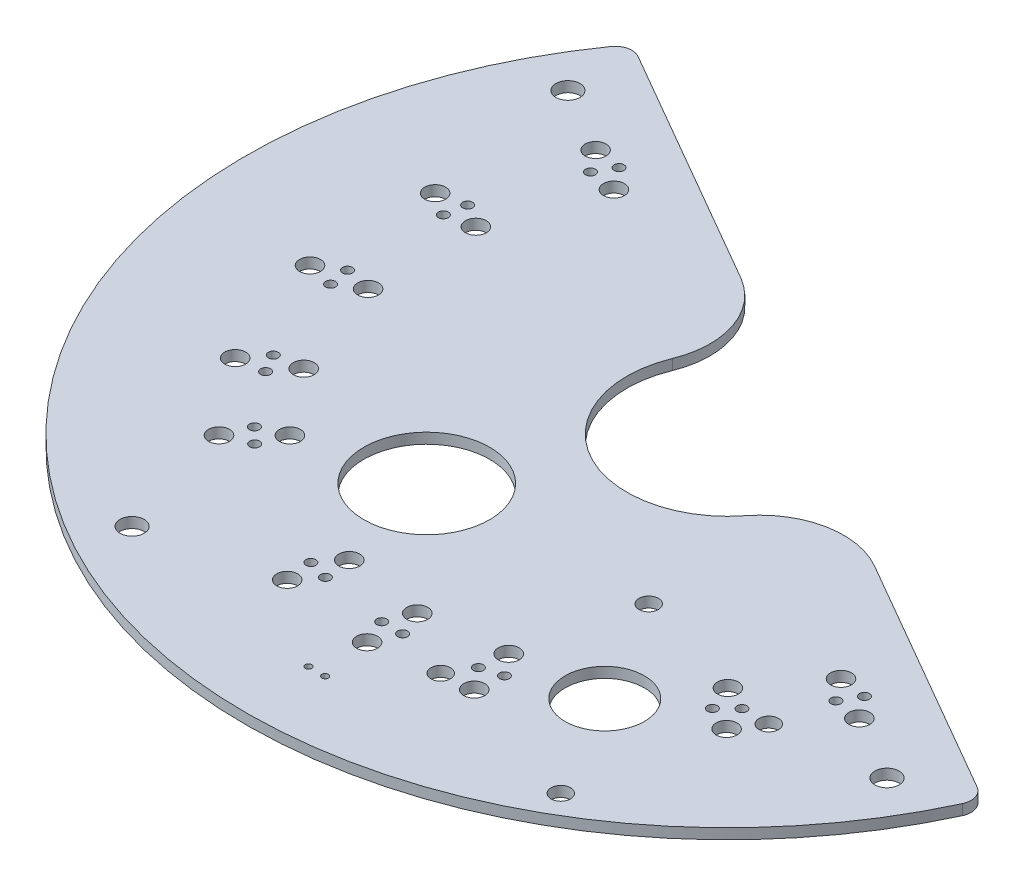
SolidWorks part; units mm, degrees
ref_plane "Front Plane" through (0, 0, 0) normal (0, 0, 1) x (1, 0, 0)
ref_plane "Top Plane" through (0, 0, 0) normal (0, 1, 0) x (1, 0, 0)
ref_plane "Right Plane" through (0, 0, 0) normal (1, 0, 0) x (0, 0, -1)
sketch "Sketch1" plane through (0, 0, 0) normal (0, 1, 0) x (1, 0, 0)
  line L0 (0, 50.8) -> (0, 59.6199) construction
  line L1 (0, 50.8) -> (11.3081, 50.8) construction
  line L2 (0, 0) -> (0, 47) construction
  line L3 (0, 0) -> (-46.286, 8.1615) construction
  line L4 (0, 0) -> (0, 47) construction
  line L5 (0, 0) -> (-46.286, -8.1615) construction
  line L6 (-35.6665, -35.9809) -> (-43.3836, -40.2586) construction
  line L7 (-13.202, -48.8223) -> (-8.5263, -41.3397) construction
  line L8 (34.9566, -37.7798) -> (30.8142, -29.9892) construction
  line L9 (12.3219, -50.1988) -> (12.3219, -41.3754) construction
  circle A0 centre (0, 0) radius 50.8 construction
  circle A1 centre (0, 0) radius 15.24
  circle A2 centre (0, 0) radius 73.025
  circle A3 centre (0, 50.8) radius 6.3 construction
  circle A4 centre (25.4, 43.9941) radius 6.3 construction
  circle A5 centre (43.9941, 25.4) radius 6.3 construction
  circle A6 centre (50.8, 0) radius 6.3 construction
  circle A7 centre (43.9941, -25.4) radius 6.3 construction
  circle A8 centre (25.4, -43.9941) radius 6.3 construction
  circle A9 centre (0, -50.8) radius 6.3 construction
  circle A10 centre (-25.4, -43.9941) radius 6.3 construction
  circle A11 centre (-43.9941, -25.4) radius 6.3 construction
  circle A12 centre (-50.8, 0) radius 6.3 construction
  circle A13 centre (-43.9941, 25.4) radius 6.3 construction
  circle A14 centre (-25.4, 43.9941) radius 6.3 construction
  circle A15 centre (0, 50.8) radius 1.585 construction
  circle A16 centre (-1.585, 50.8) radius 0.75
  circle A17 centre (1.585, 50.8) radius 0.75
  circle A18 centre (0, 50.8) radius 3.8 construction
  circle A19 centre (0, 54.6) radius 1.585
  circle A20 centre (0, 47) radius 1.585
  circle A21 centre (47.285, 27.3) radius 1.585
  circle A22 centre (43.2016, 26.7727) radius 0.75
  circle A23 centre (44.7866, 24.0273) radius 0.75
  circle A24 centre (40.7032, 23.5) radius 1.585
  circle A25 centre (47.285, -27.3) radius 1.585
  circle A26 centre (44.7866, -24.0273) radius 0.75
  circle A27 centre (43.2016, -26.7727) radius 0.75
  circle A28 centre (40.7032, -23.5) radius 1.585
  circle A29 centre (0, -54.6) radius 1.585
  circle A30 centre (1.585, -50.8) radius 0.75
  circle A31 centre (-1.585, -50.8) radius 0.75
  circle A32 centre (0, -47) radius 1.585
  circle A33 centre (-47.285, -27.3) radius 1.585
  circle A34 centre (-43.2016, -26.7727) radius 0.75
  circle A35 centre (-44.7866, -24.0273) radius 0.75
  circle A36 centre (-40.7032, -23.5) radius 1.585
  circle A37 centre (-47.285, 27.3) radius 1.585
  circle A38 centre (-44.7866, 24.0273) radius 0.75
  circle A39 centre (-43.2016, 26.7727) radius 0.75
  circle A40 centre (-40.7032, 23.5) radius 1.585
  circle A41 centre (25.4, 43.9941) radius 20
  circle A42 centre (-16.3207, -29.2429) radius 9.525
  circle A43 centre (25.4, -43.9941) radius 6
  circle A44 centre (-46.286, 8.1615) radius 1.585
  circle A45 centre (-50.3035, 7.2604) radius 0.75
  circle A46 centre (-49.753, 10.3822) radius 0.75
  circle A47 centre (-53.7705, 9.4812) radius 1.585
  circle A48 centre (-46.286, -8.1615) radius 1.585
  circle A49 centre (-49.753, -10.3822) radius 0.75
  circle A50 centre (-50.3035, -7.2604) radius 0.75
  circle A51 centre (-53.7705, -9.4812) radius 1.585
  circle A52 centre (-35.6625, -35.9801) radius 6.3 construction
  circle A53 centre (-35.6625, -35.9801) radius 1.585 construction
  circle A54 centre (-34.5403, -37.1015) radius 0.75
  circle A55 centre (-36.7991, -34.8717) radius 0.75
  circle A56 centre (-35.6625, -35.9801) radius 3.8 construction
  circle A57 centre (-38.371, -38.6691) radius 1.585
  circle A58 centre (-32.9869, -33.3052) radius 1.585
  circle A59 centre (-13.2051, -48.8249) radius 6.3 construction
  circle A60 centre (-13.2051, -48.8249) radius 1.585 construction
  circle A61 centre (-14.7302, -48.3882) radius 0.75
  circle A62 centre (-11.6736, -49.2433) radius 0.75
  circle A63 centre (-13.2051, -48.8249) radius 3.8 construction
  circle A64 centre (-12.1398, -45.16) radius 1.585
  circle A65 centre (-14.2484, -52.4617) radius 1.585
  circle A66 centre (35.9794, -36.0227) radius 6.3 construction
  circle A67 centre (35.9794, -36.0227) radius 1.585 construction
  circle A68 centre (34.8386, -37.1251) radius 0.75
  circle A69 centre (37.1074, -34.9056) radius 0.75
  circle A70 centre (35.9794, -36.0227) radius 3.8 construction
  circle A71 centre (33.3381, -33.2676) radius 1.585
  circle A72 centre (38.6072, -38.7446) radius 1.585
  circle A73 centre (13.281, -49.0556) radius 6.3 construction
  circle A74 centre (13.281, -49.0556) radius 1.585 construction
  circle A75 centre (11.7562, -49.4935) radius 0.75
  circle A76 centre (14.8015, -48.5989) radius 0.75
  circle A77 centre (13.281, -49.0556) radius 3.8 construction
  circle A78 centre (12.2423, -45.3831) radius 1.585
  circle A79 centre (14.3234, -52.6926) radius 1.585
  point P50 (0, 0)
  point P84 (0, 0)
  dimension "D1" = 12
  dimension "D2" = 101.6
  dimension "D3" = 3.17
  dimension "D4" = 1.5
  dimension "D5" = 7.6
  dimension "D6" = 6
  dimension "D7" = 3.17
  dimension "D8" = 40
  dimension "D9" = 19.05
  dimension "D10" = 12
  dimension "D11" = 146.05
  dimension "D12" = 30.48
  dimension "D14" = 80
  dimension "D16" = 100
  dimension "D13" = 2
  dimension "D15" = 2
extrude "Boss-Extrude1" add sketch "Sketch1" against normal blind 1.5875
sketch "Sketch2" plane through (0, 0, 0) normal (0, 1, 0) x (1, 0, 0)
  line L0 (0, 0) -> (0, 66.04) construction
  line L1 (0, 0) -> (-57.1923, 33.02) construction
  circle A0 centre (0, 0) radius 66.04 construction
  circle A1 centre (0, 66.04) radius 1.8288 construction
  circle A2 centre (-57.1923, 33.02) radius 1.8288
  circle A3 centre (33.02, 57.1923) radius 1.8288
  circle A4 centre (57.1923, -33.02) radius 1.8288
  circle A5 centre (-33.02, -57.1923) radius 1.8288
  point P17 (0, 0)
  dimension "D1" = 132.08
  dimension "D2" = 3.6576
  dimension "D3" = 2
  dimension "D4" = 60
  dimension "D5" = 4
extrude "Cut-Extrude1" cut sketch "Sketch2" against normal through all
sketch "Sketch3" plane through (0, 0, 0) normal (0, 1, 0) x (1, 0, 0)
  line L0 (-57.1923, 33.02) -> (57.1923, -33.02) construction
  line L1 (-59.5338, 44.6372) -> (68.4238, -29.2392)
  line L2 (-52.7473, 40.719) -> (61.6373, -25.321) construction
  arc A0 (68.4238, -29.2392) -> (-59.5338, 44.6372) centre (0, 0) ccw
  dimension "D1" = 8.89
extrude "Cut-Extrude2" cut sketch "Sketch3" against normal through all
fillet "Fillet1" radius 12.7 2 edges at (15.165, -0.7937, -1.5098) (-6.275, -0.7937, -13.8882)
fillet "Fillet2" radius 2.54 2 edges at (67.2161, -0.7937, 28.542) (-58.3261, -0.7937, -43.9399)
sketch "Sketch4" plane through (0, 0, 0) normal (0, 1, 0) x (1, 0, 0)
  line L0 (0, 0) -> (0, -73.025) construction
  arc A0 (-59.6949, 42.0615) -> (66.2738, -30.6666) centre (0, 0) ccw construction
  circle A1 centre (0, 0) radius 62.23 construction
  circle A2 centre (0, -62.23) radius 0.4953 construction
  circle A3 centre (1.27, -62.23) radius 0.4953
  circle A4 centre (-1.27, -62.23) radius 0.4953
  dimension "D1" = 0.9906
  dimension "D4" = 124.46
  dimension "D2" = 2
  dimension "D3" = 2
extrude "Cut-Extrude3" cut sketch "Sketch4" against normal through all
sketch "Sketch5" plane through (0, -1.5875, 0) normal (0, -1, 0) x (1, 0, 0)
  line L0 (33.4313, 14.6608) -> (45.1943, 21.4369)
  line L1 (-40.1796, 32.3083) -> (-48.041, 37.733)
  line L2 (15.6014, 49.5771) -> (17.3468, 49.1279)
  line L3 (-6.1735, 49.3058) -> (-8.3807, 60.5102)
  line L4 (-41.6699, 31.1262) -> (-49.1143, 36.3251)
  line L5 (-38.0572, 34.939) -> (-40.1796, 32.3083)
  line L6 (-4.1515, 51.8458) -> (-5.603, 60.8303)
  line L7 (-36.3633, 33.6798) -> (-38.9306, 30.7899)
  line L8 (-29.8352, -23.5566) -> (-22.3061, -19.4834)
  line L9 (-30.0614, -20.8271) -> (-34.9366, -23.4915)
  line L10 (-29.8352, -23.5566) -> (-36.3971, -27.1309)
  line L11 (-34.9366, -23.4915) -> (-36.367, -20.936)
  line L12 (-36.3971, -27.1309) -> (-39.4597, -21.5215)
  line L13 (17.3468, 49.1279) -> (20.9545, 57.3815)
  line L14 (28.0125, 9.134) -> (57.698, 26.2729)
  line L15 (-44.2736, 0.0193) -> (-49.7221, -0.0508)
  line L16 (-41.9942, 2.6626) -> (-49.6429, 2.6024)
  line L17 (-15.6685, 49.2436) -> (-34.8805, 38.3227)
  line L18 (-33.2785, 36.9483) -> (-15.1445, 47.1989)
  line L19 (-11.2582, 50.4483) -> (-9.7112, 50.8493)
  line L20 (-9.7112, 50.8493) -> (3.4499, 23.791)
  line L21 (-10.7343, 48.4036) -> (1.1138, 23.6295)
  line L22 (15.3579, 47.4805) -> (18.5019, 46.6477)
  line L23 (18.5019, 46.6477) -> (23.0154, 56.5863)
  line L24 (-2.4986, 49.9178) -> (-3.6572, 49.777)
  line L25 (35.0146, 38.3704) -> (33.3087, 39.6339)
  line L26 (33.581, 36.9581) -> (30.2501, 34.116)
  line L27 (33.3087, 39.6339) -> (26.2805, 33.5658)
  line L28 (30.2501, 34.116) -> (26.2079, 30.667)
  line L29 (46.9491, 22.383) -> (54.8184, 26.9567)
  line L30 (29.0015, 12.1089) -> (33.4313, 14.6608)
  line L93 (-25.3983, -18.1143) -> (-30.0614, -20.8271)
  arc A0 (1.2936, 63.3849) -> (1.2464, 61.0751) centre (1.27, 62.23) ccw
  arc A1 (-1.424, 61.0712) -> (-1.1127, 63.3883) centre (-1.27, 62.23) ccw
  arc A2 (-1.424, 61.0712) -> (-5.603, 60.8303) centre (0, 0) ccw
  arc A3 (-1.1127, 63.3883) -> (-55.1757, -31.2244) centre (0, 0) ccw
  arc A4 (54.8184, 26.9567) -> (23.0154, 56.5863) centre (0, 0) ccw
  arc A5 (-43.9682, -27.7852) -> (-54.2777, -28.0295) centre (-49.1824, -25.3982) cw
  arc A6 (11.4741, 50.7303) -> (2.0786, 51.9702) centre (0, 0) ccw
  arc A7 (26.2079, 30.667) -> (-2.5388, 40.2601) centre (0, 0) ccw
  arc A8 (2.0786, 51.9702) -> (2.1788, 49.6774) centre (1.585, 50.8) ccw
  arc A9 (-2.4986, 49.9178) -> (-2.0786, 51.9702) centre (-1.585, 50.8) ccw
  arc A10 (-48.5747, -10.856) -> (-50.8197, -11.0715) centre (-49.753, -10.3822) ccw
  arc A11 (-51.5416, -6.9775) -> (-49.3321, -6.4422) centre (-50.3035, -7.2604) ccw
  arc A12 (46.0468, 24.185) -> (44.5201, 22.7856) centre (44.7866, 24.0273) ccw
  arc A13 (41.9819, 27.1266) -> (43.9682, 27.7852) centre (43.2016, 26.7727) ccw
  arc A14 (-49.2651, 6.5292) -> (-51.5416, 6.9775) centre (-50.3035, 7.2604) ccw
  arc A15 (-50.8197, 11.0715) -> (-48.5191, 10.6827) centre (-49.753, 10.3822) ccw
  arc A16 (57.698, 26.2729) -> (1.2936, 63.3849) centre (0, 0) ccw
  arc A17 (-2.0786, 51.9702) -> (-4.1515, 51.8458) centre (0, 0) ccw
  arc A18 (-1.3689, 42.6081) -> (-3.6572, 49.777) centre (7.0837, 49.2559) cw
  arc A19 (45.1943, 21.4369) -> (44.5201, 22.7856) centre (0.205, -0.2124) ccw
  arc A20 (29.0015, 12.1089) -> (3.4499, 23.791) centre (4.4592, -7.7862) ccw
  arc A21 (28.0125, 9.134) -> (-22.3061, -19.4834) centre (4.4288, -7.9452) ccw
  arc A22 (46.9491, 22.383) -> (46.0468, 24.185) centre (0, 0) ccw
  arc A23 (43.9682, 27.7852) -> (38.3448, 35.1411) centre (0, 0) ccw
  arc A24 (-46.0468, -24.185) -> (-44.2913, -22.8579) centre (-44.7866, -24.0273) ccw
  arc A25 (-41.947, -26.9697) -> (-43.9682, -27.7852) centre (-43.2016, -26.7727) ccw
  arc A26 (41.9819, 27.1266) -> (36.8305, 33.7185) centre (0.205, -0.2124) ccw
  circle A27 centre (1.27, 62.23) radius 0.4953
  arc A28 (-43.9682, 27.7852) -> (-41.9544, 26.5331) centre (-43.2016, 26.7727) ccw
  arc A29 (-43.969, 23.0556) -> (-46.0468, 24.185) centre (-44.7866, 24.0273) ccw
  circle A30 centre (-1.27, 62.23) radius 0.4953
  arc A31 (-41.947, -26.9697) -> (-55.1757, -31.2244) centre (-49.6338, -25.7624) cw
  circle A32 centre (-26.7727, 43.2016) radius 1.27 [skipped]
  circle A33 centre (-24.0273, 44.7866) radius 1.27 [skipped]
  circle A34 centre (24.0273, 44.7866) radius 1.27 [skipped]
  circle A35 centre (26.7727, 43.2016) radius 1.27 [skipped]
  circle A36 centre (50.8, 1.585) radius 1.27 [skipped]
  circle A37 centre (50.8, -1.585) radius 1.27 [skipped]
  circle A38 centre (44.7866, -24.0273) radius 1.27 [skipped]
  circle A39 centre (43.2016, -26.7727) radius 1.27 [skipped]
  circle A40 centre (26.7727, -43.2016) radius 1.27 [skipped]
  circle A41 centre (24.0273, -44.7866) radius 1.27 [skipped]
  circle A42 centre (1.585, -50.8) radius 1.27 [skipped]
  circle A43 centre (-1.585, -50.8) radius 1.27 [skipped]
  circle A44 centre (-24.0273, -44.7866) radius 1.27 [skipped]
  circle A45 centre (-26.7727, -43.2016) radius 1.27 [skipped]
  circle A46 centre (-50.8, 1.585) radius 1.27 [skipped]
  circle A47 centre (-50.8, -1.585) radius 1.27 [skipped]
  arc A48 (-39.4597, -21.5215) -> (-44.2736, 0.0193) centre (-4.3951, -2.377) cw
  arc A49 (-38.9306, 30.7899) -> (-41.9544, 26.5331) centre (0.205, -0.2124) ccw
  arc A50 (26.2805, 33.5658) -> (-1.3689, 42.6081) centre (0, 0) ccw
  circle A51 centre (1.585, 50.8) radius 0.75
  arc A52 (-46.0468, 24.185) -> (-47.789, 20.5287) centre (0, 0) ccw
  arc A53 (10.8831, 48.5612) -> (2.1788, 49.6774) centre (0.205, -0.2124) ccw
  arc A54 (-41.6699, 31.1262) -> (-43.9682, 27.7852) centre (0, 0) ccw
  arc A55 (-8.3807, 60.5102) -> (-48.041, 37.733) centre (0, 0) ccw
  arc A56 (-36.3633, 33.6798) -> (-38.0572, 34.939) centre (-36.7887, 34.8764) ccw
  arc A57 (-43.969, 23.0556) -> (-48.5191, 10.6827) centre (0.205, -0.2124) ccw
  circle A58 centre (-1.585, 50.8) radius 0.75
  circle A59 centre (43.2016, 26.7727) radius 0.75
  arc A60 (-47.789, 20.5287) -> (-50.8197, 11.0715) centre (0, 0) ccw
  arc A61 (-51.5416, 6.9775) -> (-51.5416, -6.9775) centre (0, 0) ccw
  arc A62 (-49.2651, 6.5292) -> (-49.6429, 2.6024) centre (0.205, -0.2124) ccw
  circle A63 centre (44.7866, 24.0273) radius 0.75
  arc A64 (-50.8197, -11.0715) -> (-46.0468, -24.185) centre (0, 0) ccw
  arc A65 (-48.5747, -10.856) -> (-44.2913, -22.8579) centre (0.205, -0.2124) ccw
  circle A66 centre (-43.2016, 26.7727) radius 0.75
  circle A67 centre (-44.7866, 24.0273) radius 0.75
  circle A68 centre (-49.753, 10.3822) radius 0.75
  circle A69 centre (-50.3035, 7.2604) radius 0.75
  circle A70 centre (-50.3035, -7.2604) radius 0.75
  circle A71 centre (-49.753, -10.3822) radius 0.75
  circle A72 centre (-44.7866, -24.0273) radius 0.75
  circle A73 centre (-43.2016, -26.7727) radius 0.75
  arc A74 (1.1138, 23.6295) -> (-25.3983, -18.1143) centre (4.4592, -7.7862) ccw
  arc A75 (20.9545, 57.3815) -> (1.2464, 61.0751) centre (0, 0) ccw
  arc A76 (-2.5388, 40.2601) -> (-6.1735, 49.3058) centre (13.4353, 51.9317) cw
  arc A86 (-31.3368, 13.0383) -> (-32.985, 14.2011) centre (-31.3367, 14.7878) ccw construction
  arc A87 (-32.985, 14.2011) -> (-34.3304, 11.6344) centre (112.8254, -63.8668) ccw construction
  arc A88 (-33.9153, -16.8172) -> (-31.9293, -16.3872) centre (-32.7611, -17.3469) ccw construction
  arc A89 (-31.9293, -16.3872) -> (-32.6415, -14.9048) centre (-79.0072, -38.0929) ccw construction
  circle A91 centre (-32.7183, -17.2601) radius 0.75 construction
  arc A92 (-34.3304, 11.6344) -> (-33.9153, -16.8172) centre (-7.3644, -2.2011) ccw construction
  arc A93 (-31.3368, 13.0383) -> (-32.6415, -14.9048) centre (-7.0347, -2.0984) ccw construction
  circle A94 centre (-31.007, 15.1229) radius 0.75 construction
  circle A100 centre (-36.7887, 34.8764) radius 0.75
  arc A101 (-49.1143, 36.3251) -> (-54.2777, -28.0295) centre (0, 0) ccw
  arc A102 (-34.8805, 38.3227) -> (-33.2785, 36.9483) centre (-34.5395, 37.0993) ccw
  arc A104 (-36.367, -20.936) -> (-41.9942, 2.6626) centre (2.4474, 0.7897) cw
  arc A105 (-49.7221, -0.0508) -> (-49.3321, -6.4422) centre (0.205, -0.2124) ccw
  circle A106 centre (-34.5395, 37.0993) radius 0.75
  arc A107 (-15.1445, 47.1989) -> (-15.6685, 49.2436) centre (-14.7221, 48.3966) ccw
  circle A108 centre (-14.7221, 48.3966) radius 0.75
  arc A109 (-11.2582, 50.4483) -> (-10.7343, 48.4036) centre (-11.6806, 49.2506) ccw
  circle A110 centre (-11.6806, 49.2506) radius 0.75
  arc A111 (10.8831, 48.5612) -> (11.4741, 50.7303) centre (11.7488, 49.4904) ccw
  circle A112 centre (11.7488, 49.4904) radius 0.75
  arc A113 (15.6014, 49.5771) -> (15.3579, 47.4805) centre (14.7779, 48.6104) ccw
  circle A114 centre (14.7779, 48.6104) radius 0.75
  arc A115 (33.581, 36.9581) -> (35.0146, 38.3704) centre (34.8416, 37.1122) ccw
  circle A116 centre (34.8416, 37.1122) radius 0.75
  arc A117 (38.3448, 35.1411) -> (36.8305, 33.7185) centre (37.0875, 34.9622) ccw
  circle A118 centre (37.0875, 34.9622) radius 0.75
  point P61 (30.2501, 34.116)
  point P64 (0, 0)
  point P66 (0, 0)
  dimension "D13" = 12
  dimension "D15" = 3
extrude "Boss-Extrude2" add sketch "Sketch5" along normal blind 0.1016
sketch "Sketch6" plane through (0, -1.5875, 0) normal (0, -1, 0) x (1, 0, 0)
  line L0 (0, 0) -> (25.4, 43.9941) construction
  line L1 (25.4, 43.9941) -> (36.5125, 63.2415) construction
  circle A0 centre (25.4, 43.9941) radius 18.1937 construction
  arc A1 (66.2738, 30.6666) -> (-59.6949, -42.0615) centre (0, 0) ccw construction
  circle A2 centre (34.4969, 59.7503) radius 1.4732
  circle A3 centre (9.6438, 53.0909) radius 1.4732
  circle A4 centre (16.3031, 28.2379) radius 1.4732
  circle A5 centre (41.1562, 34.8972) radius 1.4732
  point P20 (25.4, 43.9941)
  dimension "D1" = 2.9464
extrude "Cut-Extrude4" cut sketch "Sketch6" against normal through all
